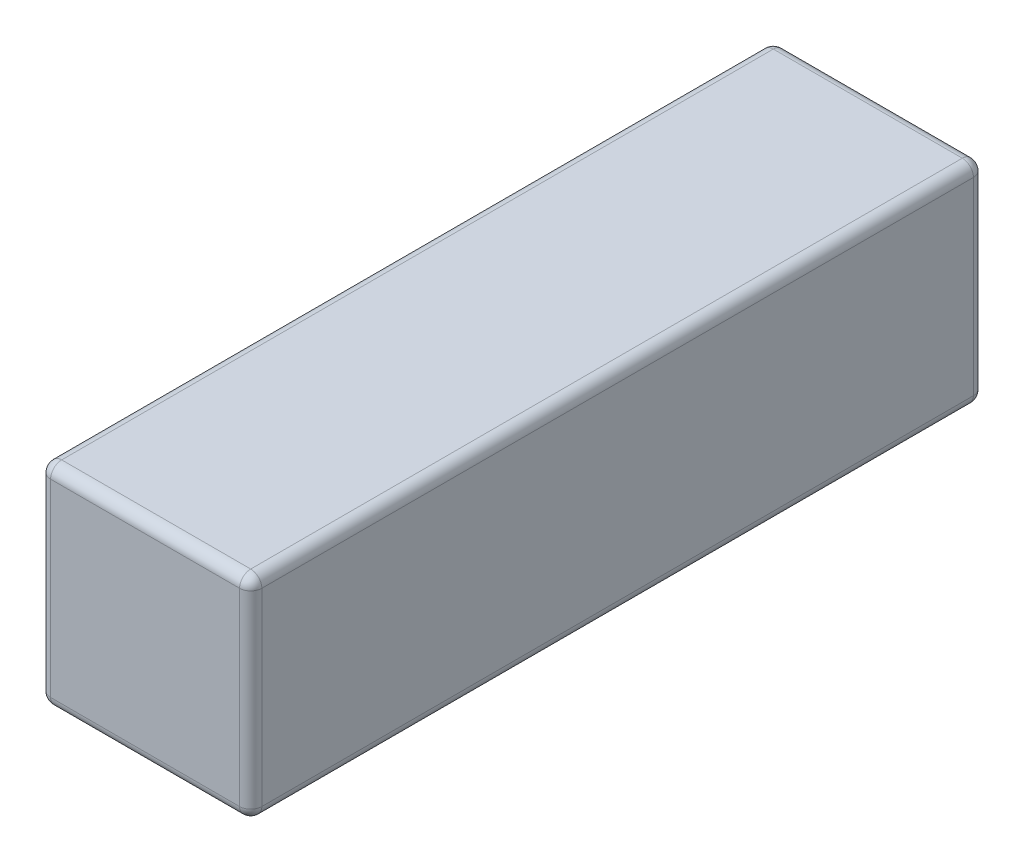
SolidWorks part; units mm, degrees
ref_plane "Front Plane" through (0, 0, 0) normal (0, 0, 1) x (1, 0, 0)
ref_plane "Top Plane" through (0, 0, 0) normal (0, 1, 0) x (1, 0, 0)
ref_plane "Right Plane" through (0, 0, 0) normal (1, 0, 0) x (0, 0, -1)
sketch "Sketch1" plane through (0, 0, 0) normal (0, 0, 1) x (1, 0, 0)
  line L1 (4.75, 4.75) -> (-4.75, 4.75)
  line L2 (4.75, 4.75) -> (4.75, -4.75)
  line L3 (4.75, -4.75) -> (-4.75, -4.75)
  line L4 (-4.75, 4.75) -> (-4.75, -4.75)
  line L5 (4.75, 4.75) -> (-4.75, -4.75) construction
  line L6 (4.75, -4.75) -> (-4.75, 4.75) construction
  point P0 (0, 0)
  dimension "D1" = 9.5
  dimension "D2" = 9.5
extrude "Boss-Extrude1" add sketch "Sketch1" along normal blind 33
fillet "Fillet1" radius 0.5 12 edges at (-4.75, 4.75, 16.5) (-4.75, -4.75, 16.5) (4.75, -4.75, 16.5) (4.75, 4.75, 16.5) (0, 4.75, 0) (4.75, 0, 0) (0, -4.75, 0) (-4.75, 0, 0) (-4.75, 0, 33) (0, -4.75, 33) (4.75, 0, 33) (0, 4.75, 33)
